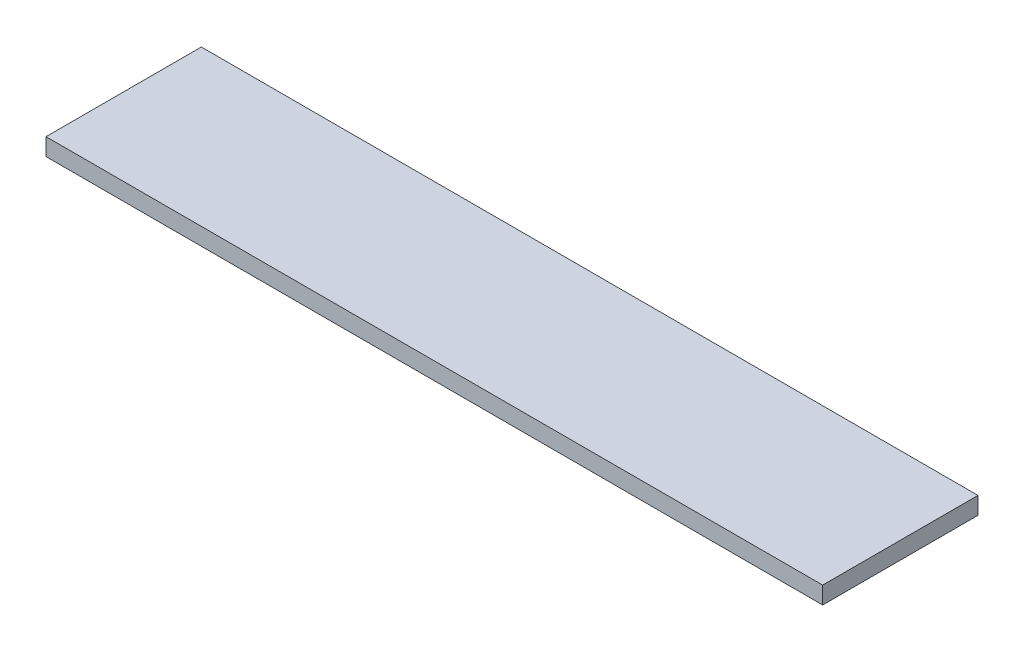
SolidWorks part; units mm, degrees
ref_plane "Front" through (0, 0, 0) normal (0, 0, 1) x (1, 0, 0)
ref_plane "Top" through (0, 0, 0) normal (0, 1, 0) x (1, 0, 0)
ref_plane "Right" through (0, 0, 0) normal (1, 0, 0) x (0, 0, -1)
sketch "Sketch8" plane through (0, 0, 0) normal (0, 0, 1) x (1, 0, 0)
  line L0 (0, 0) -> (-450, 0)
base flange "Base-Flange1" sketch "Sketch8" end condition mid plane depth 90 reverse direction no thickness 10 reverse thickness direction no bend radius 10
pattern_linear "LPattern1" [suppressed] count 2 spacing 50 count 3 spacing 50
sketch "Bend-Lines1" [suppressed] plane through (0, 0, 0) normal (0, 1, 0) x (1, 0, 0)
sketch "Bounding-Box1" [suppressed] plane through (0, 0, 0) normal (0, 1, 0) x (1, 0, 0)
sheet metal parameters "Sheet-Metal2" thickness 10 parameters "D1"=10
flat pattern "Flat-Pattern2" [suppressed]
sketch "Bend-Lines2" plane through (0, 0, 0) normal (0, 1, 0) x (1, 0, 0)
sketch3d "Bounding-Box2" [suppressed]
  line L0 (450, 90, 0) -> (0, 90, 0) construction
  line L1 (450, 0, 0) -> (0, 0, 0) construction
  line L2 (450, 90, 0) -> (450, 0, 0) construction
  line L3 (0, 90, 0) -> (0, 0, 0) construction
sheet metal parameters "Sheet-Metal3" thickness 10 parameters "D1"=10
flat pattern "Flat-Pattern3"
sketch "Bend-Lines3" plane through (0, 0, 0) normal (0, 1, 0) x (1, 0, 0)
sketch "Bounding-Box3" [suppressed] plane through (0, 0, 0) normal (0, 1, 0) x (1, 0, 0)
sheet metal parameters "Sheet-Metal4" thickness 10 parameters "D1"=10
flat pattern "Flat-Pattern4"
sketch "Bend-Lines4" plane through (0, 0, 0) normal (0, 1, 0) x (1, 0, 0)
sketch "Bounding-Box4" [suppressed] plane through (0, 0, 0) normal (0, 1, 0) x (1, 0, 0)
sheet metal parameters "Sheet-Metal5" thickness 10 parameters "D1"=10
flat pattern "Flat-Pattern5"
sketch "Bend-Lines5" plane through (0, 0, 0) normal (0, 1, 0) x (1, 0, 0)
sketch "Bounding-Box5" [suppressed] plane through (0, 0, 0) normal (0, 1, 0) x (1, 0, 0)
sheet metal parameters "Sheet-Metal6" thickness 10 parameters "D1"=10
flat pattern "Flat-Pattern6"
sketch "Bend-Lines6" plane through (0, 0, 0) normal (0, 1, 0) x (1, 0, 0)
sketch "Bounding-Box6" [suppressed] plane through (0, 0, 0) normal (0, 1, 0) x (1, 0, 0)
sheet metal parameters "Sheet-Metal7" thickness 10 parameters "D1"=10
flat pattern "Flat-Pattern7"
sketch "Bend-Lines7" plane through (0, 0, 0) normal (0, 1, 0) x (1, 0, 0)
sketch "Bounding-Box7" [suppressed] plane through (0, 0, 0) normal (0, 1, 0) x (1, 0, 0)
